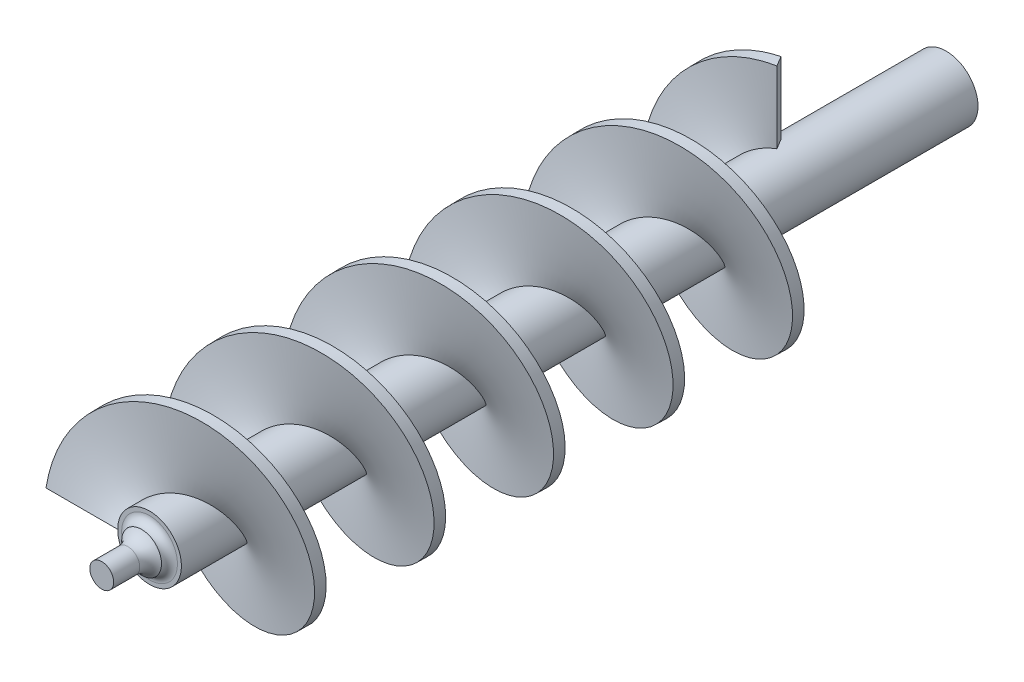
SolidWorks part; units mm, degrees
ref_plane "Front Plane" through (0, 0, 0) normal (0, 0, 1) x (1, 0, 0)
ref_plane "Top Plane" through (0, 0, 0) normal (0, 1, 0) x (1, 0, 0)
ref_plane "Right Plane" through (0, 0, 0) normal (1, 0, 0) x (0, 0, -1)
sketch "Sketch1" plane through (0, 0, 0) normal (0, 0, 1) x (1, 0, 0)
  circle A0 centre (0, 0) radius 4
  dimension "D1" = 8
extrude "Boss-Extrude1" add sketch "Sketch1" along normal blind 100
sketch "Sketch7" plane through (0, 0, 100) normal (0, 0, 1) x (1, 0, 0)
  circle A0 centre (0, 0) radius 4 construction
  circle A1 centre (0, 0) radius 4
curve "Helix/Spiral1" pitch 15 height 78.75 radius 4 centre (0, 0, 100) axis (0, 0, -1) start towards (1, 0, 0)
ref_plane "Plane1" through (-4, 0, 100) normal (0, 0.8587, -0.5125) x (-1, 0, 0)
sketch "Sketch8" plane through (-4, 0, 100) normal (0, 0.8587, -0.5125) x (-1, 0, 0)
  line L1 (0, 0) -> (9, 0)
  line L2 (0, 0) -> (0, -1.5)
  line L3 (0, -1.5) -> (9, -1.5)
  line L4 (9, 0) -> (9, -1.5)
  dimension "D1" = 9
  dimension "D2" = 1.5
sweep "Sweep1" add profiles "Sketch8" path "Helix/Spiral1"
sketch "Sketch11" plane through (0, 0, 0) normal (0, 0, -1) x (-1, 0, 0)
  line L1 (-1.9449, 1.8) -> (1.9449, 1.8)
  line L3 (-1.9449, -1.8) -> (1.9449, -1.8)
  line L5 (-3.373, 1.8) -> (3.373, -1.8) construction
  line L6 (-3.373, -1.8) -> (3.373, 1.8) construction
  arc A0 (-1.9449, 1.8) -> (-1.9449, -1.8) centre (0, 0) ccw
  arc A1 (1.9449, -1.8) -> (1.9449, 1.8) centre (0, 0) ccw
  dimension "D1" = 5.3
  dimension "D2" = 3.6
extrude "Cut-Extrude1" cut sketch "Sketch11" against normal blind 7
sketch "Sketch12" plane through (0, 0, 100) normal (0, 0, 1) x (1, 0, 0)
  circle A0 centre (0, 0) radius 2.5
  dimension "D1" = 5
extrude "Boss-Extrude2" add sketch "Sketch12" along normal blind 1
sketch "Sketch13" plane through (0, 0, 101) normal (0, 0, 1) x (1, 0, 0)
  circle A0 centre (0, 0) radius 1.5
  dimension "D1" = 3
extrude "Boss-Extrude3" add sketch "Sketch13" along normal blind 5
fillet "Fillet1" radius 2 1 edges at (1.5, 0, 101)
fillet "Fillet2" radius 1 1 edges at (2.5, 0, 100)
